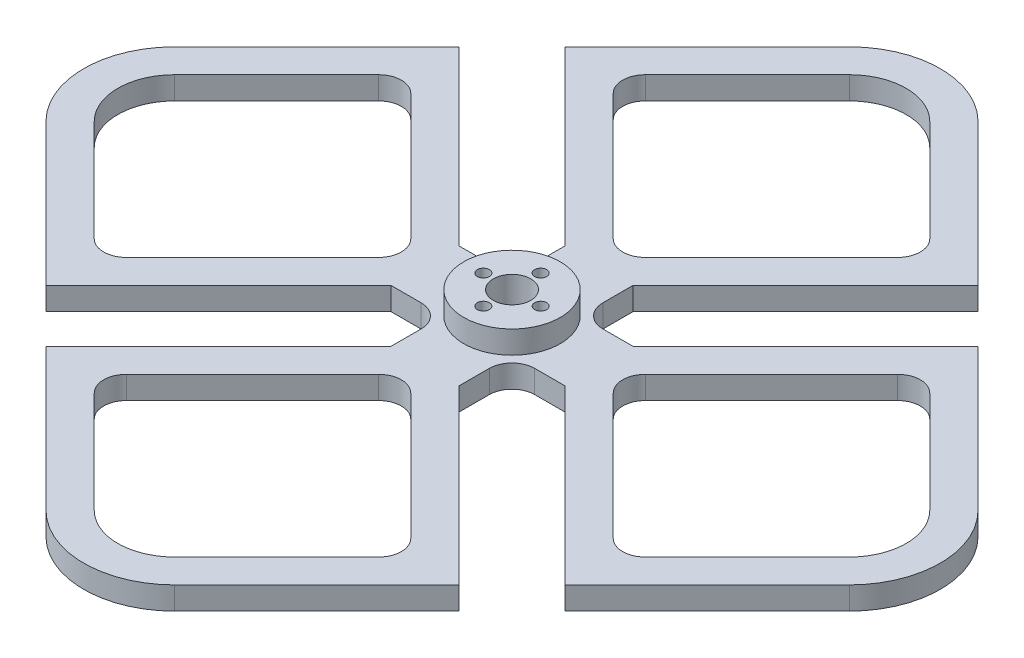
SolidWorks part; units mm, degrees
ref_plane "Front Plane" through (0, 0, 0) normal (0, 0, 1) x (1, 0, 0)
ref_plane "Top Plane" through (0, 0, 0) normal (0, 1, 0) x (1, 0, 0)
ref_plane "Right Plane" through (0, 0, 0) normal (1, 0, 0) x (0, 0, -1)
sketch "Sketch4" plane through (0, 0, 0) normal (0, 1, 0) x (1, 0, 0)
  line L8 (14.7955, 0) -> (72.4487, -57.6532)
  line L9 (14.7955, 0) -> (72.4487, 57.6532)
  line L10 (72.4487, -57.6532) -> (130.102, 0)
  line L11 (72.4487, 57.6532) -> (130.102, 0)
  line L13 (0, 9.525) -> (24.3205, 9.525)
  line L14 (0, 9.525) -> (0, -9.525)
  line L15 (0, -9.525) -> (24.3205, -9.525)
  line L16 (24.3205, 9.525) -> (24.3205, -9.525)
  dimension "D1" = 81.534
  dimension "D2" = 14.7955
  dimension "D3" = 19.05
extrude "Boss-Extrude5" add sketch "Sketch4" along normal blind 6.35 contours L9 L16 L8 L10 L11 | L16 L9 L8 | L14 L15 L8 L9 L13 region at (21.1455, 0, 0) region at (9.9723, 0, 0) region at (73.1586, 0, 0)
sketch "Sketch6" plane through (0, 0, 0) normal (0, 0, 1) x (1, 0, 0)
  line L0 (0, 0) -> (0, 27.64) construction
fillet "Fillet1" radius 25.4 1 edges at (130.102, 3.175, 0)
sketch "Sketch12" plane through (0, 6.35, 0) normal (0, 1, 0) x (1, 0, 0)
  line L14 (72.4487, -44.1829) -> (105.4063, -11.2253)
  line L15 (105.4063, 11.2253) -> (72.4487, 44.1829)
  line L16 (72.4487, 44.1829) -> (28.2659, 0)
  line L20 (28.2659, 0) -> (72.4487, -44.1829)
  line L21 (72.4487, -44.1829) -> (105.4063, -11.2253)
  line L22 (105.4063, 11.2253) -> (72.4487, 44.1829)
  line L23 (72.4487, 44.1829) -> (28.2659, 0)
  line L27 (28.2659, 0) -> (72.4487, -44.1829)
  arc A2 (105.4063, -11.2253) -> (105.4063, 11.2253) centre (94.181, 0) ccw
  arc A3 (105.4063, -11.2253) -> (105.4063, 11.2253) centre (94.181, 0) ccw
  dimension "D1" = 9.525
extrude "Cut-Extrude3" cut sketch "Sketch12" against normal through all
sketch "Sketch11" plane through (0, 0, 0) normal (0, -1, 0) x (1, 0, 0)
  line L7 (72.4487, 57.6532) -> (72.4487, 53.1631)
  line L8 (34.3487, 19.5532) -> (34.3487, 15.0631)
  line L9 (34.3487, -15.0631) -> (34.3487, -19.5532)
  line L10 (72.4487, -53.1631) -> (72.4487, -57.6532)
  line L14 (72.4487, -53.1631) -> (109.8964, -15.7154)
  line L15 (109.8964, 15.7154) -> (72.4487, 53.1631)
  line L16 (72.4487, 53.1631) -> (25.6356, 6.35)
  line L17 (25.6356, 6.35) -> (3.175, 6.35)
  line L18 (3.175, 6.35) -> (3.175, -6.35)
  line L19 (3.175, -6.35) -> (25.6356, -6.35)
  line L20 (25.6356, -6.35) -> (72.4487, -53.1631)
  line L23 (72.4487, 53.1631) -> (34.3487, 15.0631)
  line L27 (34.3487, -15.0631) -> (72.4487, -53.1631)
  line L28 (72.4487, -57.6532) -> (112.1415, -17.9605)
  line L29 (112.1415, 17.9605) -> (72.4487, 57.6532)
  line L30 (72.4487, 57.6532) -> (24.3205, 9.525)
  line L31 (24.3205, 9.525) -> (0, 9.525)
  line L32 (0, 9.525) -> (0, -9.525)
  line L33 (0, -9.525) -> (24.3205, -9.525)
  line L34 (24.3205, -9.525) -> (72.4487, -57.6532)
  line L37 (72.4487, 57.6532) -> (34.3487, 19.5532)
  line L41 (34.3487, -19.5532) -> (72.4487, -57.6532)
  arc A6 (109.8964, -15.7154) -> (109.8964, 15.7154) centre (94.181, 0) ccw
  arc A7 (112.1415, -17.9605) -> (112.1415, 17.9605) centre (94.181, 0) ccw
  dimension "D3" = 38.1
  dimension "D1" = 3.175
  dimension "D2" = 0
pattern_circular "CirPattern7" count 4 over 360 about axis through (0, 0, 0) along (0, 1, 0) of "Boss-Extrude5", "Fillet1", "Cut-Extrude3"
sketch "Sketch13" plane through (0, 6.35, 0) normal (0, 1, 0) x (1, 0, 0)
  circle A0 centre (0, 0) radius 13.4704
extrude "Boss-Extrude8" add sketch "Sketch13" along normal blind 6.35
sketch "Sketch1" plane through (0, 0, 0) normal (0, 1, 0) x (1, 0, 0)
  circle A0 centre (0, 0) radius 2.6905 construction
  circle A1 centre (0, 0) radius 5.227
  circle A2 centre (8, 0) radius 1.6865
  circle A6 centre (0, -8) radius 1.6865
  circle A7 centre (-8, 0) radius 1.6865
  circle A8 centre (0, 8) radius 1.6865
  point P15 (0, 0)
  dimension "D1" = 10.454
  dimension "D3" = 3.373
  dimension "D2" = 8
extrude "Cut-Extrude1" cut sketch "Sketch1" along normal through all
fillet "Fillet2" radius 6.35 16 edges at (-72.4487, 3.175, 44.1829) (-72.4487, 3.175, -44.1829) (-28.2659, 3.175, 0) (-44.1829, 3.175, -72.4487) (44.1829, 3.175, -72.4487) (0, 3.175, -28.2659) (72.4487, 3.175, -44.1829) (72.4487, 3.175, 44.1829) (28.2659, 3.175, 0) (44.1829, 3.175, 72.4487) (-44.1829, 3.175, 72.4487) (0, 3.175, 28.2659) (9.525, 3.175, -9.525) (-9.525, 3.175, -9.525) (-9.525, 3.175, 9.525) (9.525, 3.175, 9.525)
equation "\"tightTol\"= 0.005in"
equation "\"normTol\"= 0.01in"
equation "\"looseTol\"= 0.02in"
equation "\"D1@Sketch1\"=\"normTol\"+10.2mm"
equation "\"D2@Sketch1\"=8mm"
equation "\"D1@Sketch4\"=3.25-2*\"looseTol\""
equation "\"D2@Sketch4\"=9/16+\"looseTol\""
equation "\"D3@Sketch1\"=3.5mm-\"tightTol\""
